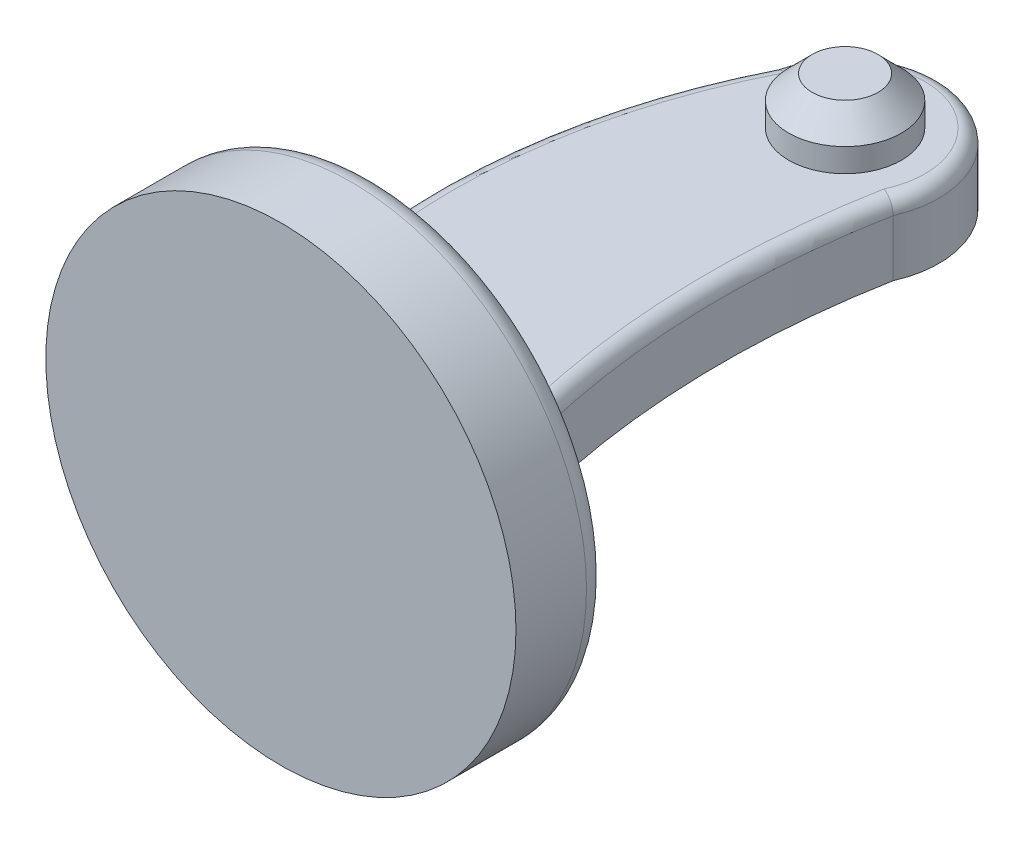
SolidWorks part; units mm, degrees
ref_plane "Front Plane" through (0, 0, 0) normal (0, 0, 1) x (1, 0, 0)
ref_plane "Top Plane" through (0, 0, 0) normal (0, 1, 0) x (1, 0, 0)
ref_plane "Right Plane" through (0, 0, 0) normal (1, 0, 0) x (0, 0, -1)
sketch "Sketch1" plane through (0, 0, 0) normal (0, 0, 1) x (1, 0, 0)
  circle A0 centre (0, 0) radius 50
extrude "Boss-Extrude1" add sketch "Sketch1" along normal blind 20
sketch "Sketch6" plane through (0, 0, 0) normal (0, 1, 0) x (1, 0, 0)
  line L1 (50, 0) -> (-50, 0) construction
  line L2 (25, 0) -> (-24.4314, 0)
  arc A0 (18.3022, 91.936) -> (-19.4578, 104.6255) centre (0, 100) ccw
  arc A1 (-19.4578, 104.6255) -> (-24.4314, 0) centre (95.6542, 46.7224) ccw
  arc A2 (18.3022, 91.936) -> (25, 0) centre (196.2299, 58.6865) ccw
extrude "Boss-Extrude2" add sketch "Sketch6" along normal mid plane 15
fillet "Fillet2" radius 5 1 edges at (50, 0, 0)
fillet "Fillet3" radius 3 6 edges at (-24.4314, 0, 0) (25, 0, 0) (0.2843, 7.5, 0) (-33.0552, 7.5, -52.8409) (6.371, 7.5, -118.9581) (15.7007, 7.5, -45.5345)
sketch "Sketch7" plane through (0, 7.5, 0) normal (0, 1, 0) x (1, 0, 0)
  circle A0 centre (0, 100) radius 12
extrude "Boss-Extrude3" add sketch "Sketch7" along normal blind 10
chamfer "Chamfer2" distance 5 angle 45 1 edges at (0, 17.5, -88)
sketch "Sketch8" plane through (0, -7.5, 0) normal (0, -1, 0) x (1, 0, 0)
  circle A0 centre (0, -100) radius 8
extrude "Cut-Extrude2" cut sketch "Sketch8" against normal blind 10
